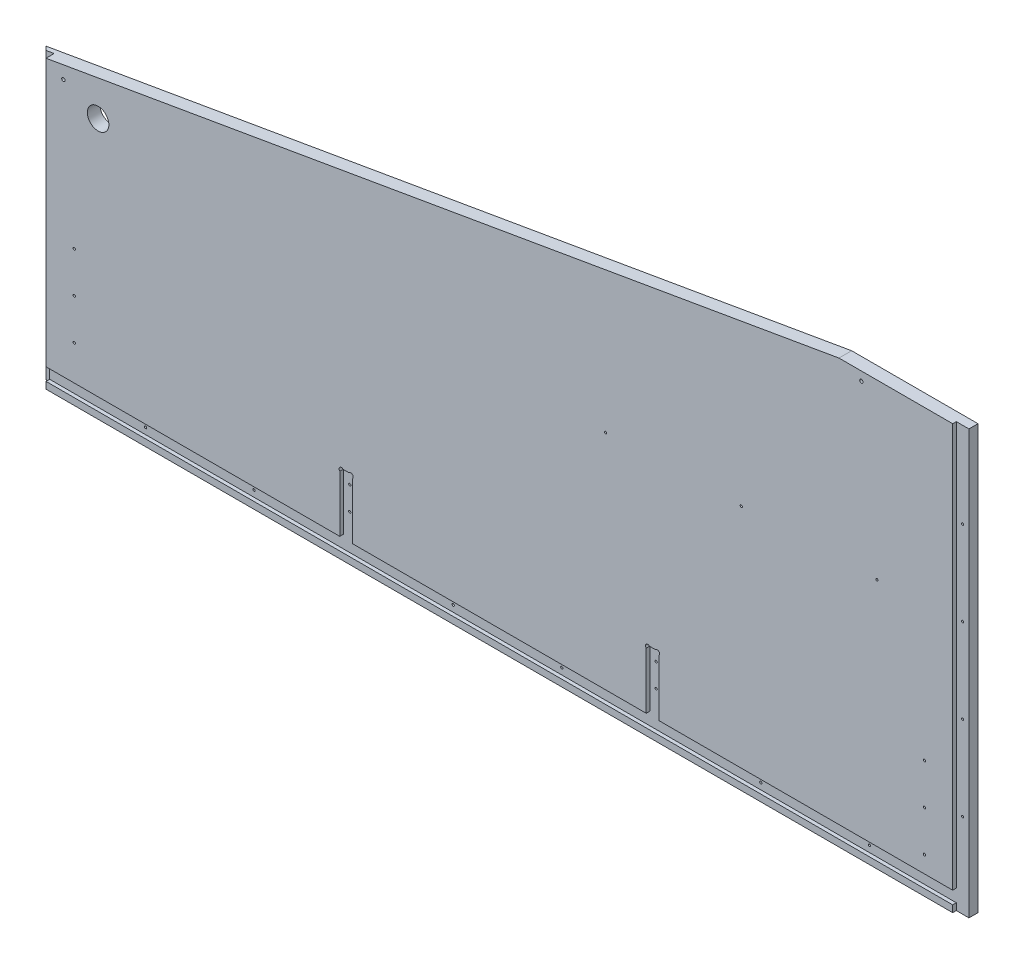
SolidWorks part; units mm, degrees
material "Maple"
ref_plane "Front Plane" through (0, 0, 0) normal (0, 0, 1) x (1, 0, 0)
ref_plane "Top Plane" through (0, 0, 0) normal (0, 1, 0) x (1, 0, 0)
ref_plane "Right Plane" through (0, 0, 0) normal (1, 0, 0) x (0, 0, -1)
sketch "Sketch1" plane through (0, 0, 0) normal (0, 0, 1) x (1, 0, 0)
  line L0 (8932.6508, -5243.5125) -> (10226.1458, -5243.5125)
  line L1 (9086.3208, -4722.0918) -> (10222.9708, -4853.7812)
  line L2 (8914.8708, -6342.0625) -> (10197.5708, -6342.0625)
  line L3 (8914.8708, -5808.6625) -> (10197.5708, -5808.6625)
  line L4 (8919.6333, -5253.0375) -> (10218.2083, -5253.0375)
  line L5 (9134.2633, -4656.1375) -> (9134.2633, -4638.3575)
  line L6 (9091.0833, -4638.3575) -> (9134.2633, -4638.3575)
  line L7 (9091.0833, -4567.2375) -> (9091.0833, -4638.3575)
  line L8 (9134.2633, -4656.1375) -> (9581.3033, -4656.1375)
  line L9 (9091.0833, -4567.2375) -> (9624.4833, -4567.2375)
  line L10 (9581.3033, -4656.1375) -> (9581.3033, -4638.3575)
  line L11 (9581.3033, -4638.3575) -> (9624.4833, -4638.3575)
  line L12 (9624.4833, -4567.2375) -> (9624.4833, -4638.3575)
  line L13 (8932.6508, -5225.7325) -> (9344.9775, -5225.7325)
  line L14 (8932.6508, -5256.2125) -> (8932.6508, -5243.5125)
  line L15 (8911.6958, -5256.2125) -> (8932.6508, -5256.2125)
  line L16 (8914.8708, -4722.0918) -> (9086.3208, -4722.0918)
  line L17 (8911.6958, -4715.5913) -> (8932.6508, -4715.5913)
  line L18 (8914.8708, -6342.0625) -> (8914.8708, -5808.6625)
  line L19 (12082.9917, -4722.0918) -> (10946.3417, -4853.7812)
  line L20 (12236.6617, -5243.5125) -> (10943.1667, -5243.5125)
  line L21 (10951.1042, -5253.0375) -> (12249.6792, -5253.0375)
  line L22 (10838.3917, -5656.2625) -> (11308.2917, -5656.2625)
  line L23 (10838.3917, -5719.7625) -> (11308.2917, -5719.7625)
  line L24 (10838.3917, -5742.5368) -> (11308.2917, -5742.5368)
  line L25 (10806.6417, -6342.0625) -> (11340.0417, -6342.0625)
  line L26 (10803.4667, -6335.7125) -> (11343.2167, -6335.7125)
  line L27 (10803.4667, -6317.9325) -> (11343.2167, -6317.9325)
  line L28 (10943.1667, -5225.7325) -> (11376.4483, -5225.7325)
  line L29 (11506.7292, -4754.5625) -> (10806.6417, -4827.5875)
  line L30 (11506.7292, -4567.2375) -> (11506.7292, -4754.5625)
  line L31 (10806.6417, -4567.2375) -> (10806.6417, -4827.5875)
  line L32 (10806.6417, -4567.2375) -> (11506.7292, -4567.2375)
  line L33 (10235.6708, -6329.3625) -> (10245.1958, -6329.3625)
  line L34 (10245.1958, -6329.3625) -> (10254.7208, -6278.5625)
  line L35 (10302.3458, -6329.3625) -> (10311.8708, -6278.5625)
  line L36 (10302.3458, -6329.3625) -> (10292.8208, -6329.3625)
  line L37 (10245.1958, -5821.3625) -> (10254.7208, -5872.1625)
  line L38 (10235.6708, -5821.3625) -> (10245.1958, -5821.3625)
  line L39 (10292.8208, -5821.3625) -> (10302.3458, -5821.3625)
  line L40 (10302.3458, -5821.3625) -> (10311.8708, -5872.1625)
  line L41 (10235.6708, -5821.3625) -> (10235.6708, -6329.3625)
  line L42 (10254.7208, -5872.1625) -> (10254.7208, -6278.5625)
  line L43 (10311.8708, -5872.1625) -> (10311.8708, -6278.5625)
  line L44 (10292.8208, -5821.3625) -> (10292.8208, -6329.3625)
  line L45 (8932.6508, -5225.7325) -> (8932.6508, -4715.5913)
  line L46 (8911.6958, -4715.5913) -> (8911.6958, -5256.2125)
  line L47 (8914.8708, -5248.275) -> (8914.8708, -4722.0918)
  line L48 (8919.6333, -5253.0375) -> (8914.8708, -5248.275)
  line L49 (8914.8708, -5145.0875) -> (8937.426, -5145.0875)
  line L50 (8914.8708, -5202.2375) -> (8937.426, -5202.2375)
  line L51 (10838.3917, -5656.2625) -> (10838.3917, -5719.7625)
  line L52 (10832.0417, -5736.1868) -> (10856.1717, -5736.1868)
  line L53 (10806.6417, -6342.0625) -> (10806.6417, -5818.7368)
  line L54 (10832.0417, -5649.9125) -> (10856.1717, -5649.9125)
  line L55 (10832.0417, -5726.1125) -> (10856.1717, -5726.1125)
  line L56 (10806.6417, -5818.7368) -> (10833.9015, -5818.7368)
  line L57 (10832.0417, -5806.0442) -> (10851.6815, -5806.0442)
  line L58 (10856.1717, -5801.5541) -> (10856.1717, -5736.1868)
  line L59 (10838.3917, -5814.2467) -> (10838.3917, -5742.5368)
  line L60 (10832.0417, -5806.0442) -> (10832.0417, -5736.1868)
  line L61 (10803.4667, -6317.9325) -> (10803.4667, -6335.7125)
  line L62 (10197.5708, -5808.6625) -> (10197.5708, -6342.0625)
  line L63 (9762.3842, -6348.4125) -> (9762.3842, -5802.3125)
  line L64 (9780.1642, -6348.4125) -> (9762.3842, -6348.4125)
  line L65 (9780.1642, -5802.3125) -> (9780.1642, -6348.4125)
  line L66 (9762.3842, -5802.3125) -> (9780.1642, -5802.3125)
  line L67 (9332.2775, -6348.4125) -> (9332.2775, -5802.3125)
  line L68 (9332.2775, -6348.4125) -> (9350.0575, -6348.4125)
  line L69 (9350.0575, -5802.3125) -> (9350.0575, -6348.4125)
  line L70 (9332.2775, -5802.3125) -> (9350.0575, -5802.3125)
  line L71 (9993.8374, -6061.075) -> (9993.8374, -6045.2418)
  line L72 (9998.5999, -6065.8375) -> (10014.4331, -6065.8375)
  line L73 (9998.5999, -6084.8875) -> (10014.4331, -6084.8875)
  line L74 (9993.8374, -6105.4832) -> (9993.8374, -6089.65)
  line L75 (9974.7874, -6105.4832) -> (9974.7874, -6089.65)
  line L76 (9954.1917, -6084.8875) -> (9970.0249, -6084.8875)
  line L77 (9974.7874, -6061.075) -> (9974.7874, -6045.2418)
  line L78 (9954.1917, -6065.8375) -> (9970.0249, -6065.8375)
  line L79 (10793.9417, -6237.2875) -> (10816.4969, -6237.2875)
  line L80 (10793.9417, -6294.4375) -> (10816.4969, -6294.4375)
  line L81 (10856.1717, -5649.9125) -> (10856.1717, -5726.1125)
  line L82 (10832.0417, -5726.1125) -> (10832.0417, -5649.9125)
  line L83 (10226.1458, -5225.7325) -> (10226.1458, -5243.5125)
  line L84 (10205.1908, -5257.8) -> (10205.1908, -4844.2499)
  line L85 (10230.9083, -4844.2499) -> (10230.9083, -5257.8)
  line L86 (10205.1908, -5257.8) -> (10230.9083, -5257.8)
  line L87 (10205.1908, -4844.2499) -> (10230.9083, -4844.2499)
  line L88 (10946.3417, -5176.8375) -> (10968.8969, -5176.8375)
  line L89 (9349.4676, -5141.9125) -> (9358.2674, -5141.9125)
  line L90 (10946.3417, -5119.6875) -> (10968.8969, -5119.6875)
  line L91 (9929.011, -4660.9635) -> (10066.0807, -4660.9635)
  line L92 (9929.011, -4678.7435) -> (10066.0807, -4678.7435)
  line L93 (10943.1667, -5225.7325) -> (10943.1667, -5243.5125)
  line L94 (10946.3417, -5248.275) -> (10951.1042, -5253.0375)
  line L95 (10946.3417, -5257.8063) -> (10946.3417, -4849.0188)
  line L96 (10964.1217, -5257.8) -> (10964.1217, -4844.2499)
  line L97 (10938.4042, -4844.2499) -> (10938.4042, -5257.8)
  line L98 (10938.4042, -5257.8) -> (10964.1217, -5257.8)
  line L99 (10964.1217, -4844.2499) -> (10938.4042, -4844.2499)
  line L100 (10344.8908, -4560.8875) -> (10369.0208, -4560.8875)
  line L101 (10344.8908, -4560.8875) -> (10369.0208, -4560.8875)
  line L102 (10800.2917, -4560.8875) -> (10824.4217, -4560.8875)
  line L103 (10200.4156, -5119.6875) -> (10222.9708, -5119.6875)
  line L104 (10200.4156, -5176.8375) -> (10222.9708, -5176.8375)
  line L105 (9344.9775, -5146.4026) -> (9344.9775, -5225.7325)
  line L106 (10344.8908, -4560.8875) -> (10344.8908, -4833.9375)
  line L107 (9792.8642, -5225.7325) -> (9792.8642, -5146.4026)
  line L108 (9362.7575, -5225.7325) -> (9775.0842, -5225.7325)
  line L109 (9680.3633, -4761.8396) -> (9680.3633, -4559.9604)
  line L110 (9656.2333, -4559.9604) -> (9680.3633, -4559.9604)
  line L111 (9656.2333, -4761.8396) -> (9680.3633, -4761.8396)
  line L112 (9656.2333, -4761.8396) -> (9656.2333, -4559.9604)
  line L113 (9779.5743, -5141.9125) -> (9788.374, -5141.9125)
  line L114 (10070.5708, -4665.4536) -> (10070.5708, -4674.2534)
  line L115 (9924.5208, -4674.2534) -> (9924.5208, -4665.4536)
  line L116 (12127.4417, -6188.3925) -> (12205.5015, -6188.3925)
  line L117 (12209.9917, -6170.6125) -> (12209.9917, -6183.9024)
  line L118 (9792.8642, -5225.7325) -> (10226.1458, -5225.7325)
  line L119 (9662.5833, -4754.5625) -> (10362.6708, -4827.5875)
  line L120 (9662.5833, -4567.2375) -> (9662.5833, -4754.5625)
  line L121 (10362.6708, -4567.2375) -> (10362.6708, -4827.5875)
  line L122 (9662.5833, -4567.2375) -> (10362.6708, -4567.2375)
  line L123 (10824.4217, -4833.9375) -> (10800.2917, -4833.9375)
  line L124 (10800.2917, -4833.9375) -> (10800.2917, -4560.8875)
  line L125 (10824.4217, -4560.8875) -> (10824.4217, -4833.9375)
  line L126 (10344.8908, -4833.9375) -> (10369.0208, -4833.9375)
  line L127 (10369.0208, -4833.9375) -> (10369.0208, -4560.8875)
  line L128 (10222.9708, -5248.275) -> (10218.2083, -5253.0375)
  line L129 (10222.9708, -5257.8063) -> (10222.9708, -4849.0188)
  line L130 (11734.6544, -5701.375) -> (11739.2301, -5701.375)
  line L131 (9362.7575, -5225.7325) -> (9362.7575, -5146.4026)
  line L132 (9775.0842, -5146.4026) -> (9775.0842, -5225.7325)
  line L133 (11761.3864, -5701.375) -> (11756.8282, -5701.375)
  line L134 (11734.6544, -5693.755) -> (11739.2301, -5693.755)
  line L135 (11761.4039, -5693.755) -> (11756.8282, -5693.755)
  line L136 (11734.6544, -5701.375) -> (11739.2301, -5701.375)
  line L137 (11744.3462, -5721.3024) -> (11744.3462, -5706.4179)
  line L138 (11751.7122, -5721.3024) -> (11751.7122, -5706.4179)
  line L139 (11740.0917, -6170.6125) -> (11740.0917, -6183.9024)
  line L140 (11689.2917, -6188.3925) -> (11822.6417, -6188.3925)
  line L141 (11689.2917, -6348.4093) -> (11689.2917, -6164.2657)
  line L142 (11689.2917, -6164.2657) -> (11746.4417, -6164.2657)
  line L143 (11746.4417, -6164.2657) -> (11746.4417, -6188.3925)
  line L144 (11689.2917, -6164.2657) -> (11746.4417, -6164.2657)
  line L145 (11340.0417, -5818.7368) -> (11340.0417, -6342.0625)
  line L146 (11290.5117, -5726.1125) -> (11314.6417, -5726.1125)
  line L147 (11290.5117, -5649.9125) -> (11290.5117, -5726.1125)
  line L148 (11340.0417, -5818.7368) -> (11312.7818, -5818.7368)
  line L149 (11314.6417, -5806.0442) -> (11295.0018, -5806.0442)
  line L150 (11290.5117, -5801.5541) -> (11290.5117, -5736.1868)
  line L151 (11308.2917, -5814.2467) -> (11308.2917, -5742.5368)
  line L152 (11314.6417, -5806.0442) -> (11314.6417, -5736.1868)
  line L153 (11290.5117, -5736.1868) -> (11314.6417, -5736.1868)
  line L154 (11848.0417, -6267.1325) -> (11962.3417, -6267.1325)
  line L155 (11962.3417, -6267.1325) -> (11962.3417, -6203.6325)
  line L156 (11343.2167, -6317.9325) -> (11343.2167, -6335.7125)
  line L157 (11365.4417, -5656.2625) -> (11365.4417, -5719.7625)
  line L158 (11365.4417, -5656.2625) -> (11479.7417, -5656.2625)
  line L159 (11778.1917, -6071.3937) -> (11802.3217, -6071.3937)
  line L160 (11314.6417, -5726.1125) -> (11314.6417, -5649.9125)
  line L161 (11314.6417, -5649.9125) -> (11290.5117, -5649.9125)
  line L162 (11308.2917, -5719.7625) -> (11308.2917, -5656.2625)
  line L163 (11689.2917, -6348.4093) -> (11713.4217, -6348.4093)
  line L164 (12203.6417, -6164.2657) -> (12260.7917, -6164.2657)
  line L165 (11713.4217, -6348.4093) -> (11713.4217, -6164.2657)
  line L166 (11695.6417, -6342.0625) -> (11695.6417, -6170.6125)
  line L167 (11695.6417, -6048.5337) -> (11699.4517, -6052.3437)
  line L168 (11822.6417, -6292.5325) -> (11822.6417, -6188.3925)
  line L169 (11695.6417, -6342.0625) -> (11695.6417, -6170.6125)
  line L170 (11848.0417, -6203.6325) -> (11962.3417, -6203.6325)
  line L171 (11848.0417, -6203.6325) -> (11848.0417, -6267.1325)
  line L172 (11987.7417, -6267.1325) -> (11987.7417, -6203.6325)
  line L173 (11784.5417, -6077.7437) -> (11784.5417, -6141.2438)
  line L174 (11517.8417, -5656.2625) -> (11632.1417, -5656.2625)
  line L175 (11632.1417, -5656.2625) -> (11632.1417, -5719.7625)
  line L176 (11632.1417, -5719.7625) -> (11517.8417, -5719.7625)
  line L177 (11517.8417, -5719.7625) -> (11517.8417, -5656.2625)
  line L178 (11692.4667, -6028.2137) -> (11692.4667, -6045.9937)
  line L179 (11695.6417, -5979.3188) -> (11718.1969, -5979.3188)
  line L180 (11695.6417, -5922.1687) -> (11718.1969, -5922.1687)
  line L181 (11821.0415, -5722.9375) -> (11821.0415, -5943.6)
  line L182 (11687.7042, -5651.5) -> (11701.9917, -5651.5)
  line L183 (11687.7042, -5651.5) -> (11687.7042, -6055.5251)
  line L184 (11687.7042, -6055.5251) -> (11701.9917, -6055.5251)
  line L185 (11701.9917, -6055.5251) -> (11701.9917, -5651.5)
  line L186 (11695.6417, -6055.2013) -> (11695.6417, -5649.595)
  line L187 (11695.6417, -5656.2625) -> (11695.6417, -6048.5337)
  line L188 (11695.6417, -6170.6125) -> (11740.0917, -6170.6125)
  line L189 (12203.6417, -6164.2657) -> (12203.6417, -6188.3925)
  line L190 (12254.4417, -6342.0625) -> (12254.4417, -6170.6125)
  line L191 (12129.0419, -5943.6) -> (12129.0419, -5722.9375)
  line L192 (12254.4417, -6048.5337) -> (12250.6317, -6052.3437)
  line L193 (12257.6167, -6045.9937) -> (12257.6167, -6028.2137)
  line L194 (12248.0917, -5651.5) -> (12262.3792, -5651.5)
  line L195 (12262.3792, -5651.5) -> (12262.3792, -6055.5251)
  line L196 (12262.3792, -6055.5251) -> (12248.0917, -6055.5251)
  line L197 (12248.0917, -6055.5251) -> (12248.0917, -5651.5)
  line L198 (12254.4417, -6141.2438) -> (12254.4417, -6077.7437)
  line L199 (12236.6617, -6164.2657) -> (12260.7917, -6164.2657)
  line L200 (12102.0417, -6267.1325) -> (11987.7417, -6267.1325)
  line L201 (11330.1865, -6237.2875) -> (11352.7417, -6237.2875)
  line L202 (11330.1865, -6294.4375) -> (11352.7417, -6294.4375)
  line L203 (11474.6617, -5851.8425) -> (11492.4417, -5851.8425)
  line L204 (11474.6617, -5808.6625) -> (11474.6617, -5851.8425)
  line L205 (11403.5417, -5808.6625) -> (11474.6617, -5808.6625)
  line L206 (11492.4417, -5851.8425) -> (11492.4417, -6298.8825)
  line L207 (11403.5417, -6342.0625) -> (11403.5417, -5808.6625)
  line L208 (11474.6617, -6298.8825) -> (11492.4417, -6298.8825)
  line L209 (11474.6617, -6342.0625) -> (11474.6617, -6298.8825)
  line L210 (11403.5417, -6342.0625) -> (11474.6617, -6342.0625)
  line L211 (11619.4417, -5851.8425) -> (11601.6617, -5851.8425)
  line L212 (11601.6617, -5808.6625) -> (11601.6617, -5851.8425)
  line L213 (11530.5417, -5808.6625) -> (11601.6617, -5808.6625)
  line L214 (11619.4417, -5851.8425) -> (11619.4417, -6298.8825)
  line L215 (11530.5417, -6342.0625) -> (11530.5417, -5808.6625)
  line L216 (11619.4417, -6298.8825) -> (11601.6617, -6298.8825)
  line L217 (11601.6617, -6342.0625) -> (11601.6617, -6298.8825)
  line L218 (11530.5417, -6342.0625) -> (11601.6617, -6342.0625)
  line L219 (11479.7417, -5719.7625) -> (11479.7417, -5656.2625)
  line L220 (11365.4417, -5719.7625) -> (11479.7417, -5719.7625)
  line L221 (11778.1917, -6147.5937) -> (11802.3217, -6147.5937)
  line L222 (11802.3217, -6071.3937) -> (11802.3217, -6147.5937)
  line L223 (11778.1917, -6147.5937) -> (11778.1917, -6071.3937)
  line L224 (12254.4417, -5922.1687) -> (12231.8865, -5922.1687)
  line L225 (12254.4417, -5979.3188) -> (12231.8865, -5979.3188)
  line L226 (12254.4417, -6055.2013) -> (12254.4417, -5649.595)
  line L227 (12254.4417, -6048.5337) -> (12254.4417, -5656.2625)
  line L228 (11841.6917, -5702.2873) -> (12108.3917, -5702.2873)
  line L229 (11822.6417, -6292.5325) -> (12127.4417, -6292.5325)
  line L230 (12127.4417, -6292.5325) -> (12127.4417, -6188.3925)
  line L231 (12254.4417, -6170.6125) -> (12209.9917, -6170.6125)
  line L232 (11695.6417, -6342.0625) -> (12254.4417, -6342.0625)
  line L233 (12236.6617, -6348.4093) -> (12260.7917, -6348.4093)
  line L234 (12260.7917, -6348.4093) -> (12260.7917, -6164.2657)
  line L235 (12236.6617, -6348.4093) -> (12236.6617, -6164.2657)
  line L236 (12102.0417, -6203.6325) -> (12102.0417, -6267.1325)
  line L237 (11987.7417, -6203.6325) -> (12102.0417, -6203.6325)
  line L238 (12236.6617, -6147.5937) -> (12236.6617, -6071.3937)
  line L239 (12203.6417, -6188.3925) -> (12260.7917, -6188.3925)
  line L240 (11098.7417, -4665.4536) -> (11098.7417, -4674.2534)
  line L241 (11394.2283, -5146.4026) -> (11394.2283, -5225.7325)
  line L242 (11376.4483, -5225.7325) -> (11376.4483, -5146.4026)
  line L243 (11394.2283, -5225.7325) -> (11806.555, -5225.7325)
  line L244 (11841.6917, -5964.2502) -> (12108.3917, -5964.2502)
  line L245 (12236.6617, -6147.5937) -> (12260.7917, -6147.5937)
  line L246 (12236.6617, -5256.2125) -> (12236.6617, -5243.5125)
  line L247 (12260.7917, -6147.5937) -> (12260.7917, -6071.3937)
  line L248 (12260.7917, -6071.3937) -> (12236.6617, -6071.3937)
  line L249 (12254.4417, -6077.7437) -> (11784.5417, -6077.7437)
  line L250 (11784.5417, -6141.2438) -> (12254.4417, -6141.2438)
  line L252 (12254.4417, -5656.2625) -> (11695.6417, -5656.2625)
  line L253 (11699.4517, -6052.3437) -> (12250.6317, -6052.3437)
  line L254 (11692.4667, -6045.9937) -> (12257.6167, -6045.9937)
  line L255 (11692.4667, -6028.2137) -> (12257.6167, -6028.2137)
  line L256 (11824.335, -5146.4026) -> (11824.335, -5225.7325)
  line L257 (11811.0451, -5141.9125) -> (11819.8449, -5141.9125)
  line L258 (11244.7917, -4674.2534) -> (11244.7917, -4665.4536)
  line L259 (11806.555, -5225.7325) -> (11806.555, -5146.4026)
  line L260 (11488.9492, -4761.8396) -> (11488.9492, -4559.9604)
  line L261 (11488.9492, -4559.9604) -> (11513.0792, -4559.9604)
  line L262 (11488.9492, -4761.8396) -> (11513.0792, -4761.8396)
  line L263 (11513.0792, -4761.8396) -> (11513.0792, -4559.9604)
  line L264 (11240.3015, -4660.9635) -> (11103.2318, -4660.9635)
  line L265 (11103.2318, -4678.7435) -> (11240.3015, -4678.7435)
  line L266 (12236.6617, -5225.7325) -> (12236.6617, -4715.5913)
  line L267 (12257.6167, -4715.5913) -> (12257.6167, -5256.2125)
  line L268 (12254.4417, -5248.275) -> (12254.4417, -4722.0918)
  line L269 (12236.6617, -5225.7325) -> (11824.335, -5225.7325)
  line L270 (12035.0492, -4656.1375) -> (12035.0492, -4638.3575)
  line L271 (12078.2292, -4638.3575) -> (12035.0492, -4638.3575)
  line L272 (12078.2292, -4567.2375) -> (12078.2292, -4638.3575)
  line L273 (12035.0492, -4656.1375) -> (11588.0092, -4656.1375)
  line L274 (11544.8292, -4567.2375) -> (12078.2292, -4567.2375)
  line L275 (11588.0092, -4656.1375) -> (11588.0092, -4638.3575)
  line L276 (11544.8292, -4638.3575) -> (11588.0092, -4638.3575)
  line L277 (11544.8292, -4567.2375) -> (11544.8292, -4638.3575)
  line L278 (12249.6792, -5253.0375) -> (12254.4417, -5248.275)
  line L280 (12257.6167, -5256.2125) -> (12236.6617, -5256.2125)
  line L281 (12231.8865, -5145.0875) -> (12254.4417, -5145.0875)
  line L282 (12231.8865, -5202.2375) -> (12254.4417, -5202.2375)
  line L283 (12236.6617, -4715.5913) -> (12257.6167, -4715.5913)
  line L284 (12082.9917, -4722.0918) -> (12254.4417, -4722.0918)
  line L285 (11380.9385, -5141.9125) -> (11389.7382, -5141.9125)
  circle A0 centre (8923.7608, -4778.9042) radius 1.5875
  circle A1 centre (9062.6598, -4736.3765) radius 2.3685
  circle A2 centre (9051.3958, -6281.7375) radius 22.225
  circle A3 centre (9083.1458, -6249.9875) radius 1.5875
  circle A4 centre (9083.1458, -6313.4875) radius 1.5875
  circle A5 centre (9019.6458, -6249.9875) radius 1.5875
  circle A6 centre (9019.6458, -6313.4875) radius 1.5875
  circle A7 centre (8972.3383, -5202.2375) radius 1.5875
  circle A8 centre (8923.7608, -5015.9708) radius 1.5875
  circle A9 centre (8923.7608, -5134.5042) radius 1.5875
  circle A10 centre (9054.5708, -5234.6225) radius 1.5875
  circle A11 centre (8923.7608, -4897.4375) radius 1.5875
  circle A12 centre (8972.3383, -5087.9375) radius 1.5875
  circle A13 centre (8972.3383, -5145.0875) radius 1.5875
  circle A14 centre (10847.2817, -5668.9625) radius 1.5875
  circle A15 centre (10847.2817, -5707.0625) radius 1.5875
  circle A16 centre (10847.2817, -5755.2368) radius 1.5875
  circle A17 centre (10851.4092, -6237.2875) radius 1.5875
  circle A18 centre (10851.4092, -6294.4375) radius 1.5875
  circle A19 centre (10847.2817, -5793.3442) radius 1.5875
  arc A20 (10833.9015, -5818.7368) -> (10838.3917, -5814.2467) centre (10836.1466, -5816.4918) ccw
  arc A21 (10851.6815, -5806.0442) -> (10856.1717, -5801.5541) centre (10853.9266, -5803.7992) ccw
  circle A22 centre (10882.8417, -6040.4375) radius 1.5875
  circle A23 centre (10882.8417, -6218.2375) radius 1.5875
  circle A24 centre (10882.8417, -5862.6375) radius 1.5875
  circle A25 centre (10908.2417, -6326.8225) radius 1.5875
  circle A26 centre (10908.2417, -6326.8225) radius 1.5875
  circle A27 centre (10851.4092, -6180.1375) radius 1.5875
  circle A28 centre (10815.5317, -4783.4231) radius 1.5875
  circle A29 centre (10815.5317, -4696.9488) radius 1.5875
  circle A30 centre (10815.5317, -4610.4746) radius 1.5875
  circle A31 centre (10979.1323, -4867.0082) radius 2.3685
  circle A32 centre (10190.1802, -4867.0082) radius 2.3685
  circle A33 centre (10955.2317, -4929.9812) radius 1.5875
  circle A34 centre (10955.2317, -5031.5812) radius 1.5875
  circle A35 centre (10214.0808, -4929.9812) radius 1.5875
  circle A36 centre (10214.0808, -5031.5812) radius 1.5875
  circle A37 centre (9341.1675, -6265.8625) radius 1.5875
  circle A38 centre (9771.2742, -5884.8625) radius 1.5875
  circle A39 centre (9771.2742, -6138.8625) radius 1.5875
  circle A40 centre (9771.2742, -6011.8625) radius 1.5875
  arc A41 (10036.2287, -6113.8083) -> (10051.3426, -6111.6033) centre (10042.9639, -6107.0732) ccw
  arc A42 (10051.3426, -6111.6033) -> (10051.3426, -6039.1217) centre (9984.3124, -6075.3625) ccw
  arc A43 (10051.3426, -6039.1217) -> (10036.2287, -6036.9167) centre (10042.9639, -6043.6518) ccw
  arc A44 (10034.5851, -6102.5431) -> (10034.5851, -6048.1819) centre (9984.3124, -6075.3625) ccw
  arc A45 (10034.5851, -6102.5431) -> (10036.2287, -6113.8083) centre (10042.9639, -6107.0732) ccw
  arc A46 (10036.2287, -6036.9167) -> (10034.5851, -6048.1819) centre (10042.9639, -6043.6518) ccw
  arc A47 (9945.8666, -6127.2787) -> (9948.0717, -6142.3927) centre (9952.6018, -6134.0139) ccw
  arc A48 (9948.0717, -6142.3927) -> (10020.5532, -6142.3927) centre (9984.3124, -6075.3625) ccw
  arc A49 (10020.5532, -6142.3927) -> (10022.7583, -6127.2787) centre (10016.0231, -6134.0139) ccw
  arc A50 (9957.1319, -6125.6352) -> (10011.493, -6125.6352) centre (9984.3124, -6075.3625) ccw
  arc A51 (9957.1319, -6125.6352) -> (9945.8666, -6127.2787) centre (9952.6018, -6134.0139) ccw
  arc A52 (10022.7583, -6127.2787) -> (10011.493, -6125.6352) centre (10016.0231, -6134.0139) ccw
  arc A53 (9932.3962, -6036.9167) -> (9917.2822, -6039.1217) centre (9925.661, -6043.6518) ccw
  arc A54 (9917.2822, -6039.1217) -> (9917.2822, -6111.6033) centre (9984.3124, -6075.3625) ccw
  arc A55 (9917.2822, -6111.6033) -> (9932.3962, -6113.8083) centre (9925.661, -6107.0732) ccw
  arc A56 (9934.0398, -6048.1819) -> (9934.0398, -6102.5431) centre (9984.3124, -6075.3625) ccw
  arc A57 (9934.0398, -6048.1819) -> (9932.3962, -6036.9167) centre (9925.661, -6043.6518) ccw
  arc A58 (9932.3962, -6113.8083) -> (9934.0398, -6102.5431) centre (9925.661, -6107.0732) ccw
  arc A59 (9945.8666, -6023.4463) -> (9957.1319, -6025.0898) centre (9952.6018, -6016.7111) ccw
  arc A60 (10011.493, -6025.0898) -> (10022.7583, -6023.4463) centre (10016.0231, -6016.7111) ccw
  arc A61 (10011.493, -6025.0898) -> (9957.1319, -6025.0898) centre (9984.3124, -6075.3625) ccw
  arc A62 (9948.0717, -6008.3323) -> (9945.8666, -6023.4463) centre (9952.6018, -6016.7111) ccw
  arc A63 (10020.5532, -6008.3323) -> (9948.0717, -6008.3323) centre (9984.3124, -6075.3625) ccw
  arc A64 (10022.7583, -6023.4463) -> (10020.5532, -6008.3323) centre (10016.0231, -6016.7111) ccw
  arc A65 (10005.0943, -6187.7574) -> (10096.7073, -6096.1443) centre (9984.3124, -6075.3625) ccw
  arc A66 (9993.8374, -6178.3911) -> (10005.0943, -6187.7574) centre (10003.3624, -6178.3911) ccw
  arc A67 (10001.6306, -6169.0249) -> (10077.9748, -6092.6807) centre (9984.3124, -6075.3625) ccw
  arc A68 (10087.3411, -6084.8875) -> (10077.9748, -6092.6807) centre (10087.3411, -6094.4125) ccw
  arc A69 (10001.6306, -6169.0249) -> (9993.8374, -6178.3911) centre (10003.3624, -6178.3911) ccw
  arc A70 (9963.5306, -6187.7574) -> (9974.7874, -6178.3911) centre (9965.2624, -6178.3911) ccw
  arc A71 (9871.9176, -6096.1443) -> (9963.5306, -6187.7574) centre (9984.3124, -6075.3625) ccw
  arc A72 (9881.2838, -6084.8875) -> (9871.9176, -6096.1443) centre (9881.2838, -6094.4125) ccw
  arc A73 (9890.65, -6092.6807) -> (9966.9943, -6169.0249) centre (9984.3124, -6075.3625) ccw
  arc A74 (9974.7874, -6178.3911) -> (9966.9943, -6169.0249) centre (9965.2624, -6178.3911) ccw
  arc A75 (9890.65, -6092.6807) -> (9881.2838, -6084.8875) centre (9881.2838, -6094.4125) ccw
  arc A76 (9871.9176, -6054.5807) -> (9881.2838, -6065.8375) centre (9881.2838, -6056.3125) ccw
  arc A77 (9963.5306, -5962.9676) -> (9871.9176, -6054.5807) centre (9984.3124, -6075.3625) ccw
  arc A78 (9974.7874, -5972.3339) -> (9963.5306, -5962.9676) centre (9965.2624, -5972.3339) ccw
  arc A79 (9966.9943, -5981.7001) -> (9890.65, -6058.0443) centre (9984.3124, -6075.3625) ccw
  arc A80 (9881.2838, -6065.8375) -> (9890.65, -6058.0443) centre (9881.2838, -6056.3125) ccw
  arc A81 (9966.9943, -5981.7001) -> (9974.7874, -5972.3339) centre (9965.2624, -5972.3339) ccw
  arc A82 (10077.9748, -6058.0443) -> (10087.3411, -6065.8375) centre (10087.3411, -6056.3125) ccw
  arc A83 (9993.8374, -5972.3339) -> (10001.6306, -5981.7001) centre (10003.3624, -5972.3339) ccw
  arc A84 (10077.9748, -6058.0443) -> (10001.6306, -5981.7001) centre (9984.3124, -6075.3625) ccw
  arc A85 (10087.3411, -6065.8375) -> (10096.7073, -6054.5807) centre (10087.3411, -6056.3125) ccw
  arc A86 (10096.7073, -6054.5807) -> (10005.0943, -5962.9676) centre (9984.3124, -6075.3625) ccw
  arc A87 (10005.0943, -5962.9676) -> (9993.8374, -5972.3339) centre (10003.3624, -5972.3339) ccw
  arc A88 (10014.4331, -6065.8375) -> (10018.7361, -6059.0339) centre (10014.4331, -6061.075) ccw
  arc A89 (10018.7361, -6059.0339) -> (10000.641, -6040.9388) centre (9984.3124, -6075.3625) ccw
  arc A90 (10000.641, -6040.9388) -> (9993.8374, -6045.2418) centre (9998.5999, -6045.2418) ccw
  arc A91 (9993.8374, -6061.075) -> (9998.5999, -6065.8375) centre (9998.5999, -6061.075) ccw
  arc A92 (9993.8374, -6105.4832) -> (10000.641, -6109.7862) centre (9998.5999, -6105.4832) ccw
  arc A93 (10000.641, -6109.7862) -> (10018.7361, -6091.6911) centre (9984.3124, -6075.3625) ccw
  arc A94 (10018.7361, -6091.6911) -> (10014.4331, -6084.8875) centre (10014.4331, -6089.65) ccw
  arc A95 (9998.5999, -6084.8875) -> (9993.8374, -6089.65) centre (9998.5999, -6089.65) ccw
  arc A96 (9954.1917, -6084.8875) -> (9949.8888, -6091.6911) centre (9954.1917, -6089.65) ccw
  arc A97 (9949.8888, -6091.6911) -> (9967.9839, -6109.7862) centre (9984.3124, -6075.3625) ccw
  arc A98 (9967.9839, -6109.7862) -> (9974.7874, -6105.4832) centre (9970.0249, -6105.4832) ccw
  arc A99 (9974.7874, -6089.65) -> (9970.0249, -6084.8875) centre (9970.0249, -6089.65) ccw
  arc A100 (9970.0249, -6065.8375) -> (9974.7874, -6061.075) centre (9970.0249, -6061.075) ccw
  arc A101 (9949.8888, -6059.0339) -> (9954.1917, -6065.8375) centre (9954.1917, -6061.075) ccw
  arc A102 (9967.9839, -6040.9388) -> (9949.8888, -6059.0339) centre (9984.3124, -6075.3625) ccw
  arc A103 (9974.7874, -6045.2418) -> (9967.9839, -6040.9388) centre (9970.0249, -6045.2418) ccw
  arc A104 (10096.7073, -6096.1443) -> (10087.3411, -6084.8875) centre (10087.3411, -6094.4125) ccw
  circle A105 centre (9771.2742, -6265.8625) radius 1.5875
  circle A106 centre (9341.1675, -5884.8625) radius 1.5875
  circle A107 centre (9341.1675, -6138.8625) radius 1.5875
  circle A108 centre (9341.1675, -6011.8625) radius 1.5875
  circle A109 centre (11037.2315, -4887.5494) radius 15.0812
  arc A110 (9349.4676, -5141.9125) -> (9344.9775, -5146.4026) centre (9347.2226, -5144.1576) ccw
  arc A111 (9362.7575, -5146.4026) -> (9358.2674, -5141.9125) centre (9360.5124, -5144.1576) ccw
  circle A112 centre (9946.7458, -4669.8535) radius 1.5875
  arc A113 (9924.5208, -4674.2534) -> (9929.011, -4678.7435) centre (9926.7659, -4676.4984) ccw
  circle A114 centre (11003.8092, -5176.8375) radius 1.5875
  circle A115 centre (11003.8092, -5119.6875) radius 1.5875
  circle A116 centre (10353.7808, -4696.9488) radius 1.5875
  circle A117 centre (10353.7808, -4610.4746) radius 1.5875
  circle A118 centre (10353.7808, -4783.4231) radius 1.5875
  circle A119 centre (11003.8092, -5062.5375) radius 1.5875
  circle A120 centre (9353.8675, -5160.9625) radius 1.5875
  circle A121 centre (9638.7708, -5234.6225) radius 1.5875
  circle A122 centre (9671.4733, -4724.1144) radius 1.5875
  circle A123 centre (9671.4733, -4661.3637) radius 1.5875
  circle A124 centre (9671.4733, -4598.6129) radius 1.5875
  arc A125 (9792.8642, -5146.4026) -> (9788.374, -5141.9125) centre (9790.6191, -5144.1576) ccw
  arc A126 (9779.5743, -5141.9125) -> (9775.0842, -5146.4026) centre (9777.3292, -5144.1576) ccw
  circle A127 centre (10048.3458, -4669.8535) radius 1.5875
  arc A128 (10070.5708, -4665.4536) -> (10066.0807, -4660.9635) centre (10068.3258, -4663.2086) ccw
  arc A129 (10066.0807, -4678.7435) -> (10070.5708, -4674.2534) centre (10068.3258, -4676.4984) ccw
  circle A130 centre (9997.5458, -4669.8535) radius 1.5875
  arc A131 (9929.011, -4660.9635) -> (9924.5208, -4665.4536) centre (9926.7659, -4663.2086) ccw
  circle A132 centre (10132.081, -4887.5494) radius 15.0812
  circle A133 centre (10165.5033, -5176.8375) radius 1.5875
  circle A134 centre (10165.5033, -5119.6875) radius 1.5875
  circle A135 centre (9486.3708, -5234.6225) radius 1.5875
  circle A136 centre (10165.5033, -5062.5375) radius 1.5875
  circle A137 centre (9206.9708, -5234.6225) radius 1.5875
  circle A138 centre (10070.5708, -5234.6225) radius 1.5875
  circle A139 centre (9918.1708, -5234.6225) radius 1.5875
  circle A140 centre (9783.9742, -5160.9625) radius 1.5875
  circle A141 centre (9783.9742, -5193.9825) radius 1.5875
  circle A142 centre (9353.8675, -5193.9825) radius 1.5875
  circle A143 centre (11073.3417, -6326.8225) radius 1.5875
  circle A144 centre (11073.3417, -6326.8225) radius 1.5875
  circle A145 centre (11295.2742, -6180.1375) radius 1.5875
  circle A146 centre (11295.2742, -6294.4375) radius 1.5875
  circle A147 centre (11295.2742, -6237.2875) radius 1.5875
  circle A148 centre (11975.0417, -5692.775) radius 3.4925
  circle A149 centre (11263.8417, -5862.6375) radius 1.5875
  arc A150 (11739.2301, -5701.375) -> (11744.3462, -5706.4179) centre (11748.0292, -5697.565) ccw
  arc A151 (11751.7122, -5706.4179) -> (11756.8282, -5701.375) centre (11748.0292, -5697.565) ccw
  arc A152 (11744.3462, -5721.3024) -> (11751.7122, -5721.3024) centre (11748.0292, -5725.505) ccw
  arc A153 (11734.6544, -5693.755) -> (11724.9787, -5697.565) centre (11730.5667, -5697.565) ccw
  arc A154 (11756.8282, -5693.755) -> (11739.2301, -5693.755) centre (11748.0292, -5697.565) ccw
  arc A155 (11724.9787, -5697.565) -> (11734.6544, -5701.375) centre (11730.5667, -5697.565) ccw
  arc A156 (11761.3864, -5701.375) -> (11771.0797, -5697.565) centre (11765.4842, -5697.565) ccw
  arc A157 (11771.0797, -5697.565) -> (11761.4039, -5693.755) centre (11765.4917, -5697.565) ccw
  arc A158 (11740.0917, -6183.9024) -> (11744.5818, -6188.3925) centre (11742.3367, -6186.1474) ccw
  arc A159 (12205.5015, -6188.3925) -> (12209.9917, -6183.9024) centre (12207.7466, -6186.1474) ccw
  circle A160 centre (11299.4017, -5793.3442) radius 1.5875
  arc A161 (11308.2917, -5814.2467) -> (11312.7818, -5818.7368) centre (11310.5367, -5816.4918) ccw
  arc A162 (11290.5117, -5801.5541) -> (11295.0018, -5806.0442) centre (11292.7567, -5803.7992) ccw
  circle A163 centre (11704.5317, -6314.149) radius 1.5875
  circle A164 centre (11748.9817, -6208.7125) radius 1.5875
  circle A165 centre (11263.8417, -6218.2375) radius 1.5875
  circle A166 centre (11263.8417, -6040.4375) radius 1.5875
  circle A167 centre (11238.4417, -6326.8225) radius 1.5875
  circle A168 centre (11238.4417, -6326.8225) radius 1.5875
  circle A169 centre (11299.4017, -5668.9625) radius 1.5875
  circle A170 centre (11299.4017, -5707.0625) radius 1.5875
  circle A171 centre (11726.7567, -6179.5025) radius 1.5875
  circle A172 centre (11704.5317, -6199.3198) radius 1.5875
  circle A173 centre (11748.9817, -6272.2125) radius 1.5875
  circle A174 centre (11704.5317, -6256.7344) radius 1.5875
  circle A175 centre (11299.4017, -5755.2368) radius 1.5875
  circle A176 centre (11913.4467, -6301.4225) radius 1.5875
  circle A177 centre (11790.2567, -6301.4225) radius 1.5875
  circle A178 centre (11793.4317, -6128.5437) radius 1.5875
  circle A179 centre (11753.1092, -5865.0188) radius 1.5875
  circle A180 centre (11809.9417, -6037.1038) radius 1.5875
  circle A181 centre (11809.9417, -6037.1038) radius 1.5875
  circle A182 centre (11753.1092, -5922.1687) radius 1.5875
  circle A183 centre (11975.0417, -5973.7625) radius 3.4925
  circle A184 centre (11975.0417, -6037.1038) radius 1.5875
  circle A185 centre (11753.1092, -5979.3188) radius 1.5875
  circle A186 centre (11975.0417, -6037.1038) radius 1.5875
  arc A187 (11841.6917, -5702.2873) -> (11821.0415, -5722.9375) centre (11841.6917, -5722.9375) ccw
  circle A188 centre (11811.5292, -5833.2687) radius 3.4925
  arc A189 (11821.0415, -5943.6) -> (11841.6917, -5964.2502) centre (11841.6917, -5943.6) ccw
  circle A190 centre (12196.9742, -5865.0188) radius 1.5875
  arc A191 (12129.0419, -5722.9375) -> (12108.3917, -5702.2873) centre (12108.3917, -5722.9375) ccw
  circle A192 centre (12036.6367, -6301.4225) radius 1.5875
  circle A193 centre (12159.8267, -6301.4225) radius 1.5875
  circle A194 centre (12138.5542, -5833.2687) radius 3.4925
  circle A195 centre (12197.2917, -5761.0375) radius 15.0812
  circle A196 centre (11793.4317, -6090.4437) radius 1.5875
  circle A197 centre (12196.9742, -5922.1687) radius 1.5875
  arc A198 (12108.3917, -5964.2502) -> (12129.0419, -5943.6) centre (12108.3917, -5943.6) ccw
  circle A199 centre (12196.9742, -5979.3188) radius 1.5875
  circle A200 centre (12201.1017, -6272.2125) radius 1.5875
  circle A201 centre (12245.5517, -6314.149) radius 1.5875
  circle A202 centre (12245.5517, -6256.7344) radius 1.5875
  circle A203 centre (12201.1017, -6208.7125) radius 1.5875
  circle A204 centre (12223.3267, -6179.5025) radius 1.5875
  circle A205 centre (12245.5517, -6199.3198) radius 1.5875
  circle A206 centre (11171.7667, -4669.8535) radius 1.5875
  circle A207 centre (11222.5667, -4669.8535) radius 1.5875
  arc A208 (11240.3015, -4678.7435) -> (11244.7917, -4674.2534) centre (11242.5466, -4676.4984) ccw
  circle A209 centre (11385.3383, -5193.9825) radius 1.5875
  circle A210 centre (12106.6527, -4736.3765) radius 2.3685
  circle A211 centre (12140.1417, -6037.1038) radius 1.5875
  circle A212 centre (12140.1417, -6037.1038) radius 1.5875
  circle A213 centre (12245.5517, -6090.4437) radius 1.5875
  circle A214 centre (12245.5517, -6128.5437) radius 1.5875
  circle A215 centre (11385.3383, -5160.9625) radius 1.5875
  arc A216 (11824.335, -5146.4026) -> (11819.8449, -5141.9125) centre (11822.0899, -5144.1576) ccw
  arc A217 (11811.0451, -5141.9125) -> (11806.555, -5146.4026) centre (11808.8001, -5144.1576) ccw
  circle A218 centre (11815.445, -5193.9825) radius 1.5875
  circle A219 centre (11815.445, -5160.9625) radius 1.5875
  circle A220 centre (11530.5417, -5234.6225) radius 1.5875
  circle A221 centre (11962.3417, -5234.6225) radius 1.5875
  arc A222 (11244.7917, -4665.4536) -> (11240.3015, -4660.9635) centre (11242.5466, -4663.2086) ccw
  circle A223 centre (11682.9417, -5234.6225) radius 1.5875
  circle A224 centre (11497.8392, -4724.1144) radius 1.5875
  circle A225 centre (11497.8392, -4661.3637) radius 1.5875
  circle A226 centre (11497.8392, -4598.6129) radius 1.5875
  circle A227 centre (11120.9667, -4669.8535) radius 1.5875
  arc A228 (11103.2318, -4660.9635) -> (11098.7417, -4665.4536) centre (11100.9867, -4663.2086) ccw
  arc A229 (11098.7417, -4674.2534) -> (11103.2318, -4678.7435) centre (11100.9867, -4676.4984) ccw
  circle A230 centre (12196.9742, -5202.2375) radius 1.5875
  circle A231 centre (12245.5517, -5015.9708) radius 1.5875
  circle A232 centre (12245.5517, -5134.5042) radius 1.5875
  circle A233 centre (12114.7417, -5234.6225) radius 1.5875
  circle A234 centre (12245.5517, -4897.4375) radius 1.5875
  circle A235 centre (12245.5517, -4778.9042) radius 1.5875
  circle A236 centre (12196.9742, -5087.9375) radius 1.5875
  circle A237 centre (12196.9742, -5145.0875) radius 1.5875
  circle A238 centre (11098.7417, -5234.6225) radius 1.5875
  circle A239 centre (11251.1417, -5234.6225) radius 1.5875
  arc A240 (11380.9385, -5141.9125) -> (11376.4483, -5146.4026) centre (11378.6934, -5144.1576) ccw
  arc A241 (11394.2283, -5146.4026) -> (11389.7382, -5141.9125) centre (11391.9833, -5144.1576) ccw
sketch "CabSideLeft_Outline" plane through (0, 0, 0) normal (0, 0, 1) x (1, 0, 0)
  line L0 (10946.3417, -4853.7812) -> (10946.3417, -5253.0375)
  line L2 (10946.3417, -5253.0375) -> (12254.4417, -5253.0375)
  line L4 (12254.4417, -5253.0375) -> (12254.4417, -4658.6775)
  line L5 (12254.4417, -4658.6775) -> (12077.078, -4658.6775)
  line L8 (12077.078, -4658.6775) -> (10946.3417, -4853.7812)
  dimension "CabSideLeft_Length" = 1308.1
  dimension "CabSideLeft_Front" = 399.2562
  dimension "CabSideLeft_BackHeight" = 594.36
  dimension "CabSideLeft_SlopeLength" = 1147.445
extrude "CabSideLeft_Thickness" add sketch "CabSideLeft_Outline" against normal blind 17.78
sketch "CabSideLeft_LedgeCuts" plane through (0, 0, 0) normal (0, 0, 1) x (1, 0, 0)
  line L0 (10946.3417, -5225.7325) -> (10946.3417, -5243.5125)
  line L1 (10946.3417, -5243.5125) -> (12236.6617, -5243.5125)
  line L2 (12236.6617, -5243.5125) -> (12236.6617, -5253.0375)
  line L3 (12236.6617, -5253.0375) -> (12254.4417, -5253.0375)
  line L4 (12254.4417, -5253.0375) -> (12254.4417, -4658.6775)
  line L5 (12254.4417, -4658.6775) -> (12236.6617, -4658.6775)
  line L6 (12236.6617, -4658.6775) -> (12236.6617, -5225.7325)
  line L7 (12236.6617, -5225.7325) -> (11824.335, -5225.7325)
  line L8 (11824.335, -5225.7325) -> (11824.335, -5141.9125)
  line L9 (11824.335, -5141.9125) -> (11806.555, -5141.9125)
  line L10 (11806.555, -5141.9125) -> (11806.555, -5225.7325)
  line L11 (11806.555, -5225.7325) -> (11394.2283, -5225.7325)
  line L12 (11394.2283, -5225.7325) -> (11394.2283, -5141.9125)
  line L13 (11394.2283, -5141.9125) -> (11376.4483, -5141.9125)
  line L14 (11376.4483, -5141.9125) -> (11376.4483, -5225.7325)
  line L15 (11376.4483, -5225.7325) -> (10946.3417, -5225.7325)
  line L17 (10946.3417, -5253.0375) -> (12254.4417, -5253.0375) construction
  line L18 (10946.3417, -4853.7812) -> (10946.3417, -5253.0375) construction
  line L19 (12254.4417, -4658.6775) -> (12077.078, -4658.6775) construction
  line L20 (12254.4417, -5253.0375) -> (12254.4417, -4658.6775) construction
  dimension "BottomThickness" = 17.78
  dimension "BraceThickness_1" = 17.78
  dimension "BraceThickness_2" = 17.78
  dimension "BackThickness" = 17.78
extrude "LedgeCuts_Depth" cut sketch "CabSideLeft_LedgeCuts" against normal blind 5.08
sketch "CabFrontLedgeCut" plane through (0, 0, 0) normal (0, 0, 1) x (1, 0, 0)
  line L0 (10946.3417, -4850.7134) -> (10964.1217, -4850.7134)
  line L1 (10964.1217, -4850.7134) -> (10964.1217, -5253.0375)
  line L2 (10964.1217, -5253.0375) -> (10946.3417, -5253.0375)
  line L3 (10946.3417, -5253.0375) -> (10946.3417, -4850.7134)
  line L4 (12077.078, -4658.6775) -> (10946.3417, -4853.7812) construction
  line L5 (10946.3417, -5253.0375) -> (12236.6617, -5253.0375) construction
  dimension "Front_Thickness" = 17.78
extrude "FrontLedgeCut_Depth" cut sketch "CabFrontLedgeCut" against normal blind 11.43
sketch "Sketch5" plane through (0, 0, 0) normal (0, 0, 1) x (1, 0, 0)
  circle A0 centre (11037.2315, -4887.5494) radius 15.0813
  circle A2 centre (10955.2317, -4929.9812) radius 1.5875
  circle A3 centre (10955.2317, -5031.5812) radius 1.5875
  circle A4 centre (11003.8092, -5062.5375) radius 1.5875
  circle A5 centre (11003.8092, -5119.6875) radius 1.5875
  circle A6 centre (11003.8092, -5176.8375) radius 1.5875
  circle A7 centre (11251.1417, -5234.6225) radius 1.5875
  circle A8 centre (11098.7417, -5234.6225) radius 1.5875
  circle A9 centre (11385.3383, -5160.9625) radius 1.5875
  circle A10 centre (11385.3383, -5193.9825) radius 1.5875
  circle A11 centre (11530.5417, -5234.6225) radius 1.5875
  circle A12 centre (11682.9417, -5234.6225) radius 1.5875
  circle A13 centre (11815.445, -5160.9625) radius 1.5875
  circle A14 centre (11815.445, -5193.9825) radius 1.5875
  circle A15 centre (11962.3417, -5234.6225) radius 1.5875
  circle A16 centre (12114.7417, -5234.6225) radius 1.5875
  circle A17 centre (12196.9742, -5202.2375) radius 1.5875
  circle A18 centre (12196.9742, -5145.0875) radius 1.5875
  circle A19 centre (12245.5517, -5134.5042) radius 1.5875
  circle A20 centre (12196.9742, -5087.9375) radius 1.5875
  circle A21 centre (12245.5517, -5015.9708) radius 1.5875
  circle A22 centre (12245.5517, -4897.4375) radius 1.5875
  circle A23 centre (12245.5517, -4778.9042) radius 1.5875
extrude "Cut-Extrude3" cut sketch "Sketch5" against normal up to surface (17.78 mm away) up to face at (11695.7289, -4935.4422, -17.78)
sketch "Sketch6" plane through (0, 0, 0) normal (0, 0, 1) x (1, 0, 0)
  line L0 (11376.4483, -5141.9125) -> (11378.6934, -5144.1576) construction
  line L1 (11394.2283, -5141.9125) -> (11391.9833, -5144.1576) construction
  line L2 (11806.555, -5141.9125) -> (11808.8001, -5144.1576) construction
  line L3 (11824.335, -5141.9125) -> (11822.0899, -5144.1576) construction
  line L4 (11376.4483, -5141.9125) -> (11376.4483, -5225.7325) construction
  line L5 (11394.2283, -5225.7325) -> (11394.2283, -5141.9125) construction
  line L6 (11806.555, -5141.9125) -> (11806.555, -5225.7325) construction
  line L7 (11824.335, -5225.7325) -> (11824.335, -5141.9125) construction
  circle A0 centre (11378.6934, -5144.1576) radius 3.302
  circle A1 centre (11391.9833, -5144.1576) radius 3.302
  circle A2 centre (11808.8001, -5144.1576) radius 3.302
  circle A3 centre (11822.0899, -5144.1576) radius 3.302
  dimension "D1" = 45
  dimension "D2" = 3.175
  dimension "D3" = 45
  dimension "D4" = 3.175
  dimension "D5" = 45
  dimension "D6" = 45
  dimension "D7" = 3.175
  dimension "D8" = 3.175
extrude "Cut-Extrude4" cut sketch "Sketch6" against normal up to surface (5.08 mm away) up to face at (12247.1392, -4778.9042, -5.08)
sketch "FrontBevelCut" plane through (0, -5253.0375, 0) normal (0, -1, 0) x (1, 0, 0)
  line L0 (10964.1217, 0) -> (10964.1217, -17.78) construction
  line L1 (10946.3417, -17.78) -> (12254.4417, -17.78) construction
  line L2 (10964.1217, -17.78) -> (10946.3417, -17.78) construction
  line L3 (10946.3417, -17.78) -> (10946.3417, -11.43)
  line L4 (10946.3417, -11.43) -> (10952.6917, -11.43)
  line L5 (10952.6917, -11.43) -> (10946.3417, -17.78)
  dimension "Front_Thickness" = 17.78
extrude "Cut-Extrude5" cut sketch "FrontBevelCut" against normal up to surface (594.36 mm away) up to face at (12189.3938, -4658.6775, -7.62)
sketch "Sketch8" plane through (0, 0, -17.78) normal (0, 0, -1) x (-1, 0, 0)
  line L0 (-10990.8486, -4863.9963) -> (-10986.1555, -4864.8061) construction
  line L1 (-10991.2535, -4866.3429) -> (-10990.4437, -4861.6497) construction
  line L2 (-10985.7506, -4862.4595) -> (-10986.5604, -4867.1526) construction
  line L3 (-12110.9471, -4670.728) -> (-12106.2539, -4671.5378) construction
  line L4 (-12111.352, -4673.0746) -> (-12110.5422, -4668.3815) construction
  line L5 (-12105.8491, -4669.1913) -> (-12106.6588, -4673.8844) construction
  circle A0 centre (-10988.502, -4864.4012) radius 2.3812
  circle A1 centre (-12108.6005, -4671.1329) radius 2.3812
extrude "Cut-Extrude6" cut sketch "Sketch8" against normal up to surface (17.78 mm away) up to face at (11628.432, -5098.0434, 0)
sketch "Sketch9" plane through (0, 0, 0) normal (0, 0, 1) x (1, 0, 0)
  circle A0 centre (12130.3202, -4901.4921) radius 1.5875
  circle A1 centre (11939.909, -4907.3097) radius 1.5875
  circle A2 centre (11749.4979, -4913.1273) radius 1.5875
extrude "Cut-Extrude7" cut sketch "Sketch9" against normal blind 12.7
